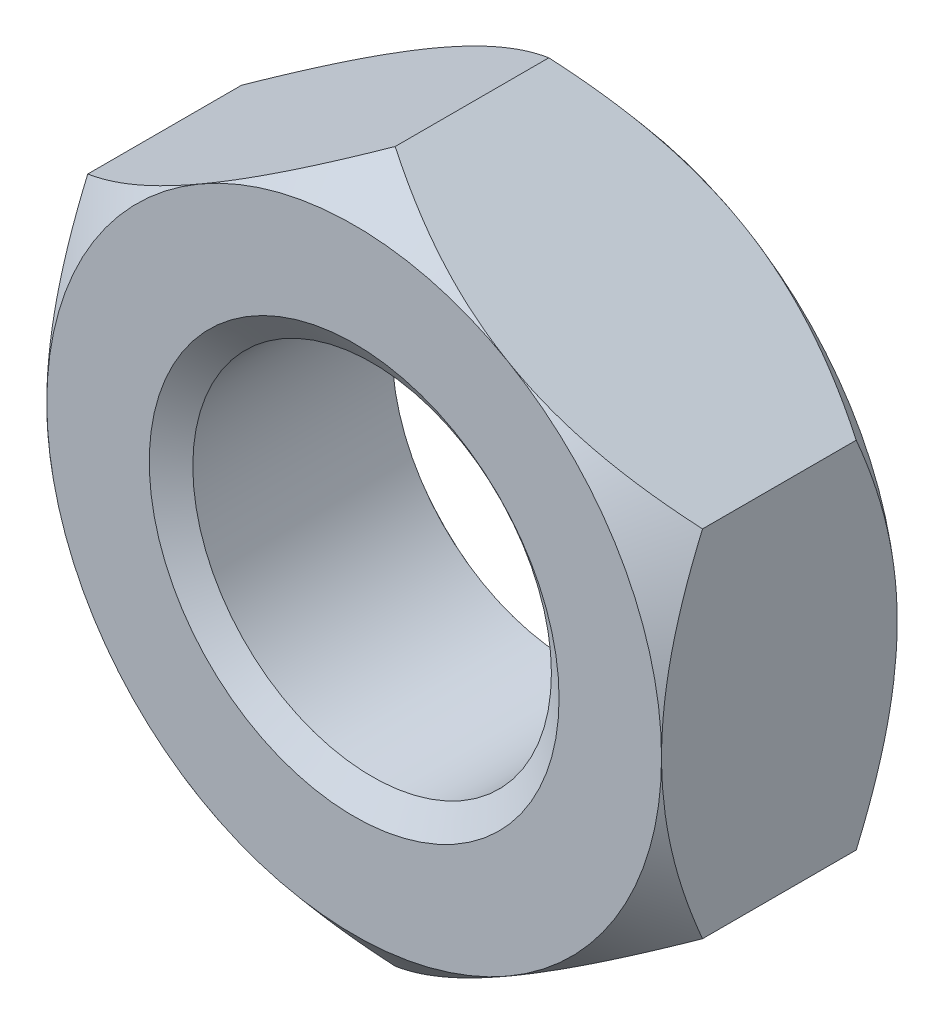
SolidWorks part; units mm, degrees
extrude "BaseNut" add sketch "BaseNutSke" against normal blind 14.605
sketch "BaseNutSke" plane through (0, 0, 0) normal (0, 0, 1) x (1, 0, 0)
  line L6 (19.05, 10.9985) -> (19.05, -10.9985)
  line L7 (-19.05, 10.9985) -> (-19.05, -10.9985)
  line L8 (19.05, 10.9985) -> (0, 21.997)
  line L9 (0, 21.997) -> (-19.05, 10.9985)
  line L10 (-19.05, -10.9985) -> (0, -21.997)
  line L11 (0, -21.997) -> (19.05, -10.9985)
  circle A0 centre (0, 0) radius 11.1125
  dimension "D2" = 19.05
  dimension "D3" = 19.05
  dimension "D1" = 120
  dimension "D4" = 19.05
cosmetic thread "ThreadCosmetic" [suppressed] parameters "Thread_major"=25.4
ref_plane "Plane1" through (0, 0, 0) normal (0, 0, 1) x (1, 0, 0)
ref_plane "Plane2" through (0, 0, 0) normal (0, 1, 0) x (1, 0, 0)
ref_plane "Plane3" through (0, 0, 0) normal (1, 0, 0) x (0, 0, -1)
sketch "Sketch4" plane through (0, 0, 0) normal (1, 0, 0) x (0, 0, -1)
  line L0 (14.605, 19.05) -> (14.1986, 19.05)
  line L1 (14.605, 19.05) -> (14.605, 34.697)
  line L2 (14.1986, 34.697) -> (14.605, 34.697)
  line L3 (14.1986, 34.697) -> (14.1986, 19.05)
  line L4 (0, 0) -> (34.925, 0) construction
  line L6 (14.605, 10.9985) -> (14.605, 21.997) construction
  line L7 (0, 19.05) -> (-12.7, 19.05)
  line L8 (0, 10.9985) -> (0, 21.997) construction
  line L9 (2.54, 21.997) -> (2.54, 34.697)
  line L10 (2.54, 34.697) -> (-12.7, 34.697)
  line L11 (-12.7, 34.697) -> (-12.7, 19.05)
  line L12 (0, 19.05) -> (2.54, 21.997)
  line L14 (0, 10.9985) -> (0, -10.9985) construction
  line L15 (14.605, 21.997) -> (0, 21.997) construction
  dimension "D1" = 19.05
  dimension "D2" = 2.54
  dimension "D3" = 12.7
  dimension "D4" = 12.7
revolve "Bearing-Face" [suppressed] cut sketch "Sketch4" angle 360 about L4
sketch "Sketch3" plane through (0, 0, 0) normal (1, 0, 0) x (0, 0, -1)
  line L0 (14.605, 19.05) -> (12.065, 21.997)
  line L1 (12.065, 21.997) -> (12.065, 34.697)
  line L2 (12.065, 34.697) -> (27.305, 34.697)
  line L3 (27.305, 34.697) -> (27.305, 19.05)
  line L4 (27.305, 19.05) -> (14.605, 19.05)
  line L5 (14.605, 10.9985) -> (14.605, 21.997) construction
  line L6 (14.605, 21.997) -> (0, 21.997) construction
  line L7 (0, 0) -> (38.6776, 0) construction
  line L8 (14.605, 0) -> (0, 0) construction
  line L9 (7.3025, 21.997) -> (7.3025, 44.222) construction
  line L10 (2.54, 34.697) -> (-12.7, 34.697)
  line L11 (-12.7, 34.697) -> (-12.7, 19.05)
  line L12 (-12.7, 19.05) -> (0, 19.05)
  line L13 (0, 19.05) -> (2.54, 21.997)
  line L14 (2.54, 21.997) -> (2.54, 34.697)
  line L16 (14.605, 21.997) -> (0, 21.997) construction
  dimension "D1" = 19.05
  dimension "D2" = 2.54
  dimension "D4" = 12.7
  dimension "D3" = 12.7
revolve "Double-Chamfer" cut sketch "Sketch3" angle 360 about L7
sketch "EndChamferSke" plane through (0, 0, 0) normal (1, 0, 0) x (0, 0, -1)
  line L0 (14.5796, 12.7) -> (13.3569, 10.9538)
  line L1 (14.6304, 12.7) -> (14.5796, 12.7)
  line L2 (14.6304, 12.7) -> (14.6304, 10.9538)
  line L3 (14.6304, 10.9538) -> (13.3569, 10.9538)
  line L6 (-0.0508, 12.7) -> (0, 12.7)
  line L7 (0, 12.7) -> (1.2227, 10.9538)
  line L9 (1.2227, 10.9538) -> (-0.0508, 10.9538)
  line L10 (-0.0508, 10.9538) -> (-0.0508, 12.7)
  line L11 (25.0375, 0) -> (38.388, 0) construction
  dimension "D1" = 35
  dimension "D2" = 0.0508
  dimension "ThreadMajor" = 12.7
  dimension "Offset1" = 14.6304
sketch "ThdSchSke" plane through (0, 0, 0) normal (0, 1, 0) x (1, 0, 0)
  line L0 (-12.7, 0.0254) -> (-11.1125, 1.137)
  line L1 (-11.1125, 1.137) -> (-5.5562, 1.137)
  line L2 (-5.5562, 1.137) -> (-5.5562, -1.0862)
  line L3 (-5.5562, -1.0862) -> (-11.1125, -1.0862)
  line L4 (-11.1125, -1.0862) -> (-12.7, 0.0254)
  line L6 (0, 1.6129) -> (0, -2.9874) construction
  line L7 (-6.35, 1.6129) -> (6.35, 1.6129) construction
  dimension "SideAngle" = 55
  dimension "D1" = 0.0254
  dimension "Thread_major" = 25.4
  dimension "OverCut" = 11.1125
  dimension "Advance" = 3.175
revolve "EndChamfer" cut sketch "EndChamferSke" angle 360 about L11
revolve "ThreadSchematic" [suppressed] cut sketch "ThdSchSke" angle 360 about L6
pattern_linear "ThdSchPat" [suppressed]
equation "\"D2@BaseNutSke\" = \"Width_flats@BaseNutSke\" / 2"
equation "\"D3@BaseNutSke\" = \"Width_flats@BaseNutSke\" / 2"
equation "\"D1@Sketch3\" = \"Width_flats@BaseNutSke\" /2"
equation "\"D2@Sketch3\" = \"Thread_major@ThreadCosmetic\" *.1"
equation "\"D1@Sketch4\" = \"D2@BaseNutSke\""
equation "\"D2@Sketch4\" = \"Thread_major@ThreadCosmetic\" *.10"
equation "\"D4@BaseNutSke\" = \"D3@BaseNutSke\""
equation "\"Thread_major@ThdSchSke\" = \"Thread_major@ThreadCosmetic\""
equation "\"Tap_drill@ThdSchSke\" = \"Thread_min@BaseNutSke\""
equation "\"OverCut@ThdSchSke\" = \"Tap_drill@ThdSchSke\" * 0.5"
equation "\"Num_threads@ThdSchPat\" = int(  ( \"Thickness@BaseNut\" - 0.002 ) / \"Advance@ThdSchSke\" + 0.999 )  + 1"
equation "\"Advance@ThdSchPat\" = ( \"Thickness@BaseNut\" - 0.002 ) /  (\"Num_threads@ThdSchPat\" - 1) 'relax it"
equation "' \"Num_threads@ThdSchPat\" = \"Num_threads@ThdSchPat\" - sgn( \"Num_threads@ThdSchPat\" - 1) '---chamfered tips only---"
equation "\"ThreadMajor@EndChamferSke\" = \"Thread_major@ThreadCosmetic\" * 0.5"
equation "\"ChamferDepth@EndChamferSke\" = (\"Thread_major@ThreadCosmetic\" - \"Thread_min@BaseNutSke\") * 0.55"
equation "\"Offset1@EndChamferSke\" = \"Thickness@BaseNut\" + 0.001"
equation "\"Offset2@EndChamferSke\" = \"Offset1@EndChamferSke\" + 0.002"
